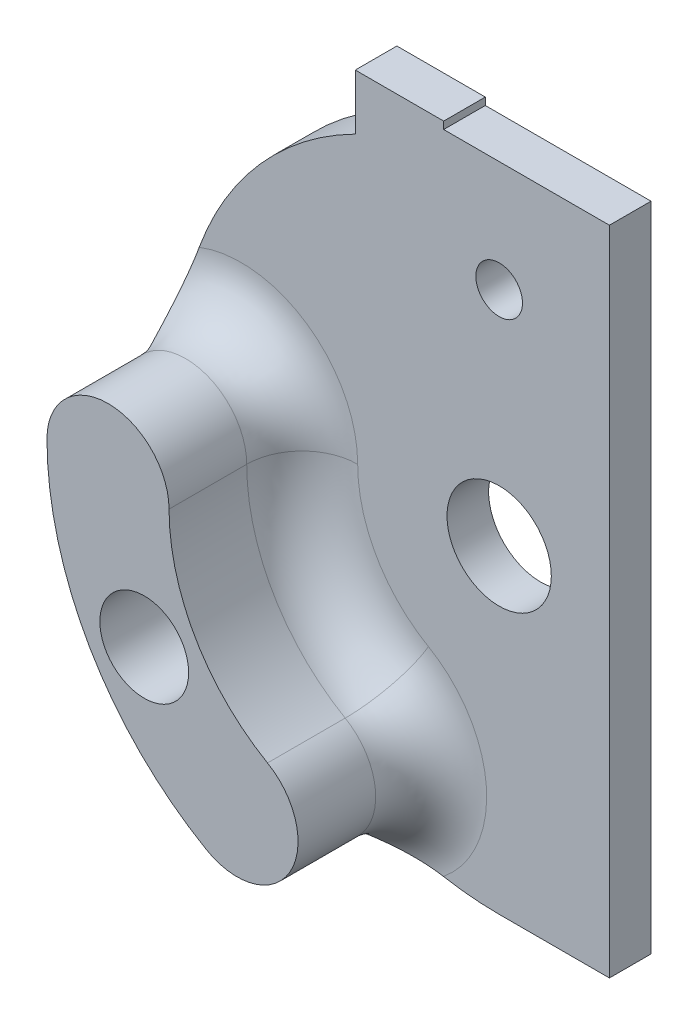
SolidWorks part; units mm, degrees
ref_plane "Front Plane" through (0, 0, 0) normal (0, 0, 1) x (1, 0, 0)
ref_plane "Top Plane" through (0, 0, 0) normal (0, 1, 0) x (1, 0, 0)
ref_plane "Right Plane" through (0, 0, 0) normal (1, 0, 0) x (0, 0, -1)
sketch "Sketch1" plane through (0, 0, 0) normal (0, 0, 1) x (1, 0, 0)
  line L0 (-16.4677, 32.588) -> (-16.4677, 38.938)
  line L1 (-0.0816, -36.5124) -> (12.6184, -36.5124)
  line L2 (12.6184, -36.5124) -> (12.6184, 1.5875)
  line L3 (-6.35, 38.938) -> (-16.4677, 38.938)
  line L4 (12.6184, 1.5875) -> (12.6184, 38.1)
  line L5 (12.6184, 38.1) -> (-6.35, 38.1)
  line L6 (-6.35, 38.1) -> (-6.35, 38.938)
  arc A0 (-0.0816, -36.5124) -> (-16.4677, 32.588) centre (0, 0) cw
  circle A1 centre (-31.115, 0) radius 5.3975 construction
  circle A2 centre (0, -31.115) radius 5.3975 construction
  circle A3 centre (0, 0) radius 5.969 construction
  circle A4 centre (0, 25.4) radius 3.302 construction
  point P17 (-6.35, 37.4081)
  point P18 (0, 0)
  point P19 (-6.35, 38.1)
  point P20 (-6.35, 38.1)
  point P21 (12.629, 38.1)
  dimension "D1" = 36.5125
  dimension "D2" = 10.795
  dimension "D3" = 10.795
  dimension "D4" = 11.938
  dimension "D7" = 31.115
  dimension "D11" = 6.604
  dimension "D13" = 0.838
  dimension "D5" = 6.35
  dimension "D6" = 12.7
  dimension "D8" = 31.115
  dimension "D9" = 6.35
  dimension "D10" = 38.1
  dimension "D12" = 25.4
extrude "Boss-Extrude1" add sketch "Sketch1" along normal blind 4.7625
sketch "Sketch4" plane through (0, 0, 4.7625) normal (0, 0, 1) x (1, 0, 0)
  circle A0 centre (0, 0) radius 5.969
  circle A1 centre (0, 25.4) radius 2.667
  dimension "D1" = 11.938
  dimension "D2" = 5.334
  dimension "D3" = 25.4
extrude "Cut-Extrude1" cut sketch "Sketch4" against normal through all
sketch "Sketch6" plane through (0, 0, 4.7625) normal (0, 0, 1) x (1, 0, 0)
  arc A0 (-36.5125, 0) -> (-22.5425, 0) centre (-29.5275, 0) cw
  arc A1 (-11.2712, -19.5224) -> (-18.2562, -31.6208) centre (-14.7637, -25.5716) cw
  arc A2 (-11.2712, -19.5224) -> (-22.5425, 0) centre (0, 0) cw
  arc A3 (-18.2562, -31.6208) -> (-36.5125, 0) centre (0, 0) cw
  dimension "D1" = 60
  dimension "D2" = 6.985
  dimension "D3" = 29.5275
  dimension "D4" = 29.5275
extrude "Boss-Extrude3" add sketch "Sketch6" along normal blind 15.24
sketch "Sketch7" [suppressed] plane through (0, 0, 26.9875) normal (0, 0, 1) x (1, 0, 0)
  circle A0 centre (-29.5275, 0) radius 5.334
  circle A1 centre (-14.7637, -25.5716) radius 5.334
fillet "Fillet1" radius 6.35 3 edges at (-8.7146, -29.0641, 4.7625) (-29.5275, 6.985, 4.7625) (-19.5224, -11.2713, 4.7625)
sketch "Sketch8" plane through (0, 0, 20.0025) normal (0, 0, 1) x (1, 0, 0)
  circle A0 centre (-25.3812, -15.0886) radius 5.08
  dimension "D1" = 29.5275
extrude "Cut-Extrude2" cut sketch "Sketch8" against normal up to surface (20.0025 mm away) up to face at (5.969, 0, 0)
